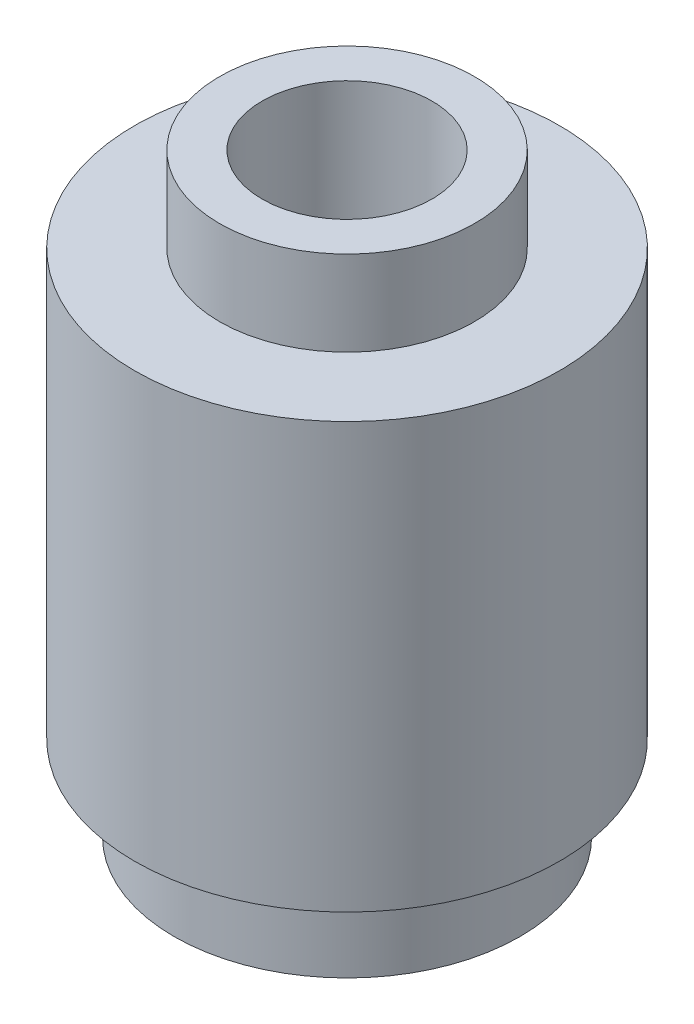
SolidWorks part; units mm, degrees
ref_plane "Front Plane" through (0, 0, 0) normal (0, 0, 1) x (1, 0, 0)
ref_plane "Top Plane" through (0, 0, 0) normal (0, 1, 0) x (1, 0, 0)
ref_plane "Right Plane" through (0, 0, 0) normal (1, 0, 0) x (0, 0, -1)
sketch "Sketch1" plane through (0, 0, 0) normal (0, 1, 0) x (1, 0, 0)
  circle A0 centre (0, 0) radius 2.5
  circle A1 centre (0, 0) radius 1.5
  circle A2 centre (0, 0) radius 2.0355
  dimension "D1" = 5
  dimension "D2" = 3
  dimension "D3" = 4.0711
extrude "Boss-Extrude1" add sketch "Sketch1" along normal blind 6 contours A0 A2 | A2 A1 region at (-2.4293, 0, 0) region at (-1.978, 0, 0)
extrude "Cut-Extrude1" cut sketch "Sketch1<3>" along normal blind 1 contours A0 A2 region at (-2.4293, 0, 0)
sketch "Sketch1<3>" plane through (0, 0, 0) normal (0, 1, 0) x (1, 0, 0) same geometry as "Sketch1"
sketch "Sketch2" plane through (0, 6, 0) normal (0, 1, 0) x (1, 0, 0)
  circle A0 centre (0, 0) radius 1.5
  circle A1 centre (0, 0) radius 1
  dimension "D1" = 2
extrude "Boss-Extrude3" add sketch "Sketch2" along normal blind 1 and the other way blind 1
equation "\"bottom\"= 5 * 2 ^ 0.5 - 3"
